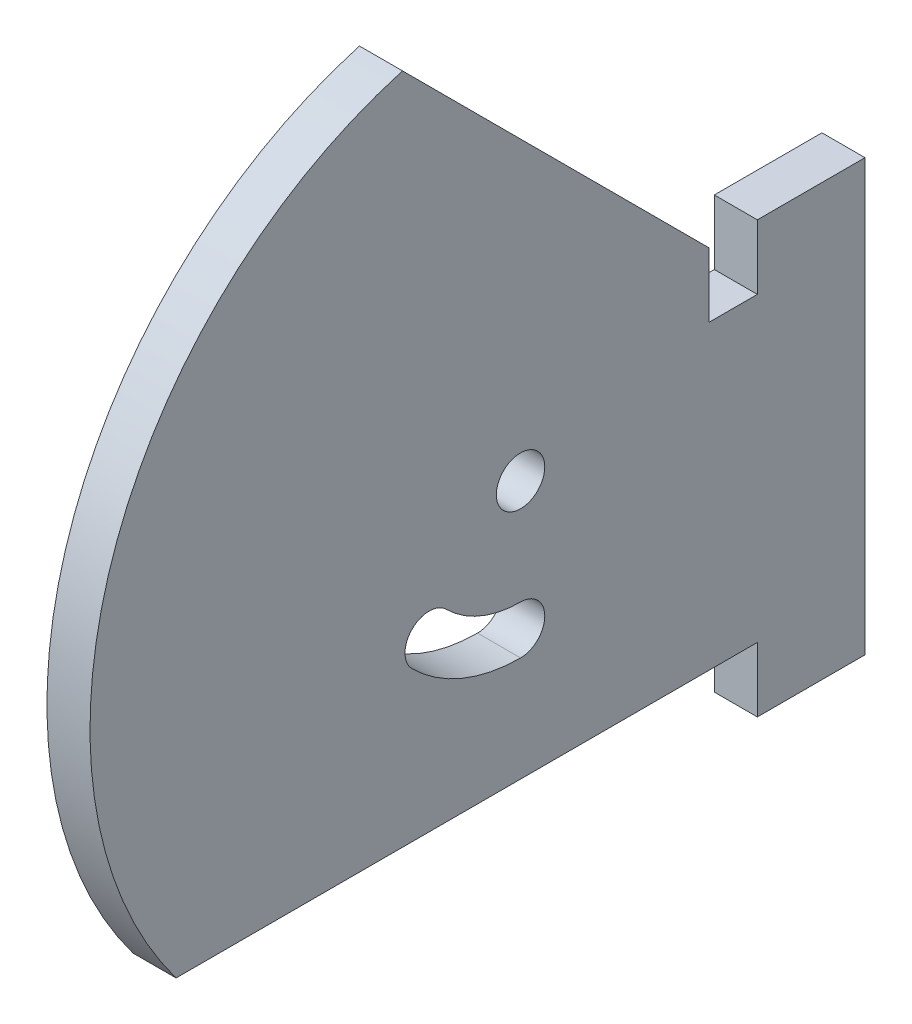
SolidWorks part; units mm, degrees
ref_plane "Front Plane" through (0, 0, 0) normal (0, 0, 1) x (1, 0, 0)
ref_plane "Top Plane" through (0, 0, 0) normal (0, 1, 0) x (1, 0, 0)
ref_plane "Right Plane" through (0, 0, 0) normal (1, 0, 0) x (0, 0, -1)
sketch "Sketch1" plane through (0, 0, 0) normal (1, 0, 0) x (0, 0, -1)
  line L0 (-16, 7) -> (16, 7) construction
  line L1 (-16, 14) -> (16, 14)
  line L2 (-16, 14) -> (-16, 0)
  line L3 (-16, 0) -> (16, 0)
  line L4 (16, 14) -> (16, 0)
  line L5 (0, 14) -> (0, 0) construction
  line L10 (0, 12) -> (-4.2426, 7.7574) construction
  line L11 (8.75, 14) -> (8.75, 17)
  line L12 (8.75, 17) -> (-5.4836, 31.2336)
  line L13 (16, 14) -> (11, 14)
  line L14 (16, 14) -> (16, 17)
  line L15 (16, 17) -> (11, 17)
  line L16 (11, 14) -> (11, 17)
  line L19 (16, 0) -> (11, 0)
  line L20 (16, 0) -> (16, -3)
  line L21 (16, -3) -> (11, -3)
  line L22 (11, 0) -> (11, -3)
  circle A2 centre (0, 12) radius 1.125
  circle A11 centre (0, 6) radius 1.125
  circle A12 centre (-4.2426, 7.7574) radius 1.125
  circle A14 centre (0, 12) radius 20
  circle A15 centre (0, 12) radius 4.875
  circle A16 centre (0, 12) radius 7.125
  point P15 (2.2212, 6.4263)
  point P18 (0, 0)
  dimension "D1" = 2.25
  dimension "D2" = 5
  dimension "D7" = 6
  dimension "D3" = 14
  dimension "D4" = 16
  dimension "D5" = 16
  dimension "D6" = 45
  dimension "D8" = 2.25
  dimension "D9" = 3
  dimension "D10" = 5
extrude "Boss-Extrude1" add sketch "Sketch1" along normal blind 2 contours A16 L1 L2 L3 L4 | L16 L1 L14 L15 | A11 A16 L1 A15 | L1 A16 A12 A15 | L1 A15 A2 | L1 A15 | L1 A16 A15 | A16 L1 L11 L12 A14 L2 | L19 L22 L21 L20 region at (0, 13.6507, -9.875) region at (0, 19.5839, 8.7986) region at (0, 15.5, -13.5) region at (0, 9.2539, -4.5361) region at (0, 14.1461, -5.6422) region at (0, 12.9977, -4.6499) region at (0, 15.1851, 0) region at (0, 11.1216, 5.7428)
